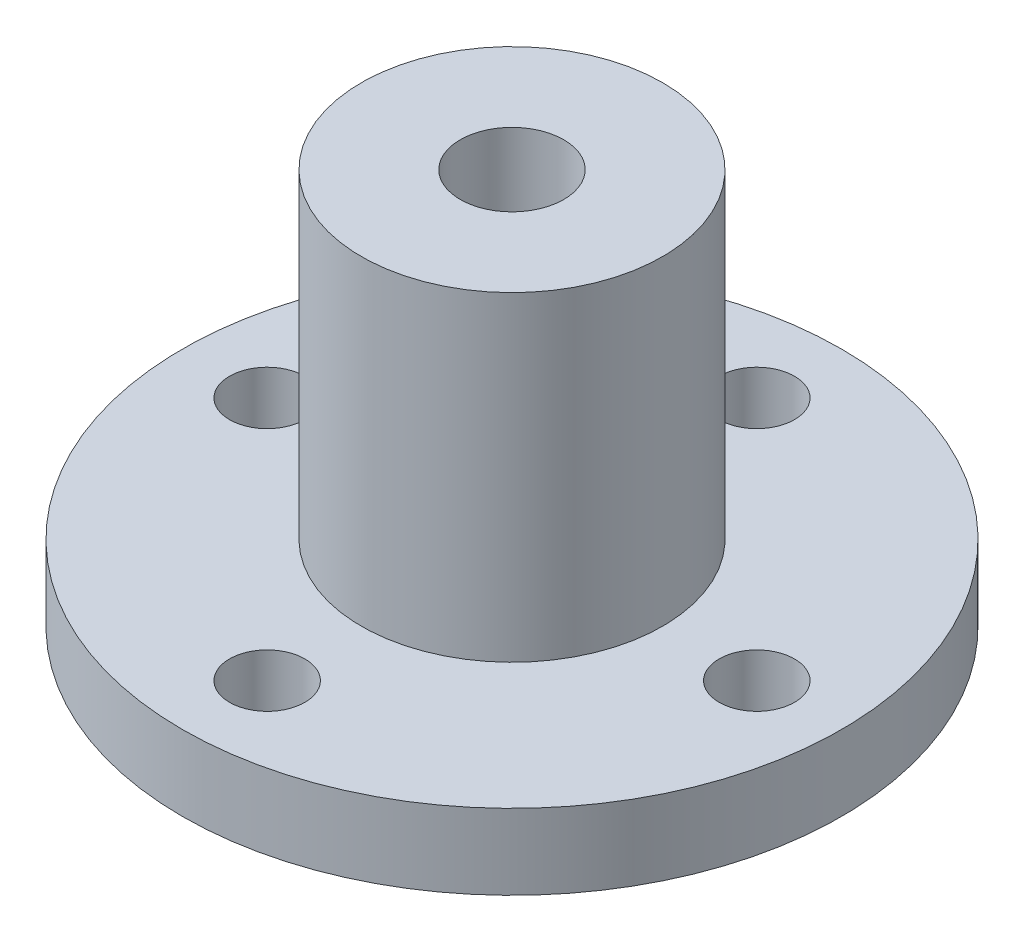
SolidWorks part; units mm, degrees
ref_plane "Front Plane" through (0, 0, 0) normal (0, 0, 1) x (1, 0, 0)
ref_plane "Top Plane" through (0, 0, 0) normal (0, 1, 0) x (1, 0, 0)
ref_plane "Right Plane" through (0, 0, 0) normal (1, 0, 0) x (0, 0, -1)
sketch "Sketch2" plane through (0, 0, 0) normal (0, 1, 0) x (1, 0, 0)
  line L0 (0, 0) -> (-10285.6085, 0) construction
  line L1 (0, 0) -> (0, 10285.6085) construction
  circle A0 centre (0, 0) radius 17.5
  circle A1 centre (0, 0) radius 13 construction
  circle A2 centre (0, 0) radius 8
  circle A3 centre (0, 13) radius 2
  circle A4 centre (13, 0) radius 2
  circle A5 centre (0, -13) radius 2
  circle A6 centre (-13, 0) radius 2
  point P20 (0, 0)
  dimension "D1" = 35
  dimension "D2" = 26
  dimension "D3" = 16
  dimension "D4" = 4
  dimension "D5" = 4
extrude "Boss-Extrude1" add sketch "Sketch2" along normal blind 4
extrude "Boss-Extrude2" add sketch "Sketch2<2>" along normal blind 21 contours A2 region at (0, 0, 0)
sketch "Sketch2<2>" plane through (0, 0, 0) normal (0, 1, 0) x (1, 0, 0) same geometry as "Sketch2"
sketch "Sketch3" plane through (0, 0, 0) normal (0, -1, 0) x (1, 0, 0)
  circle A0 centre (0, 0) radius 5.5
  dimension "D1" = 11
extrude "Cut-Extrude1" cut sketch "Sketch3" against normal blind 12
sketch "Sketch4" plane through (0, 12, 0) normal (0, -1, 0) x (1, 0, 0)
  circle A0 centre (0, 0) radius 6
  dimension "D1" = 12
extrude "Cut-Extrude2" cut sketch "Sketch4" against normal blind 1.1
sketch "Sketch5" plane through (0, 13.1, 0) normal (0, -1, 0) x (1, 0, 0)
  circle A0 centre (0, 0) radius 5.5
extrude "Cut-Extrude3" cut sketch "Sketch5" against normal blind 2.9
sketch "Sketch6" plane through (0, 16, 0) normal (0, -1, 0) x (1, 0, 0)
  circle A0 centre (0, 0) radius 2.75
  dimension "D1" = 5.5
extrude "Cut-Extrude4" cut sketch "Sketch6" against normal blind 5
